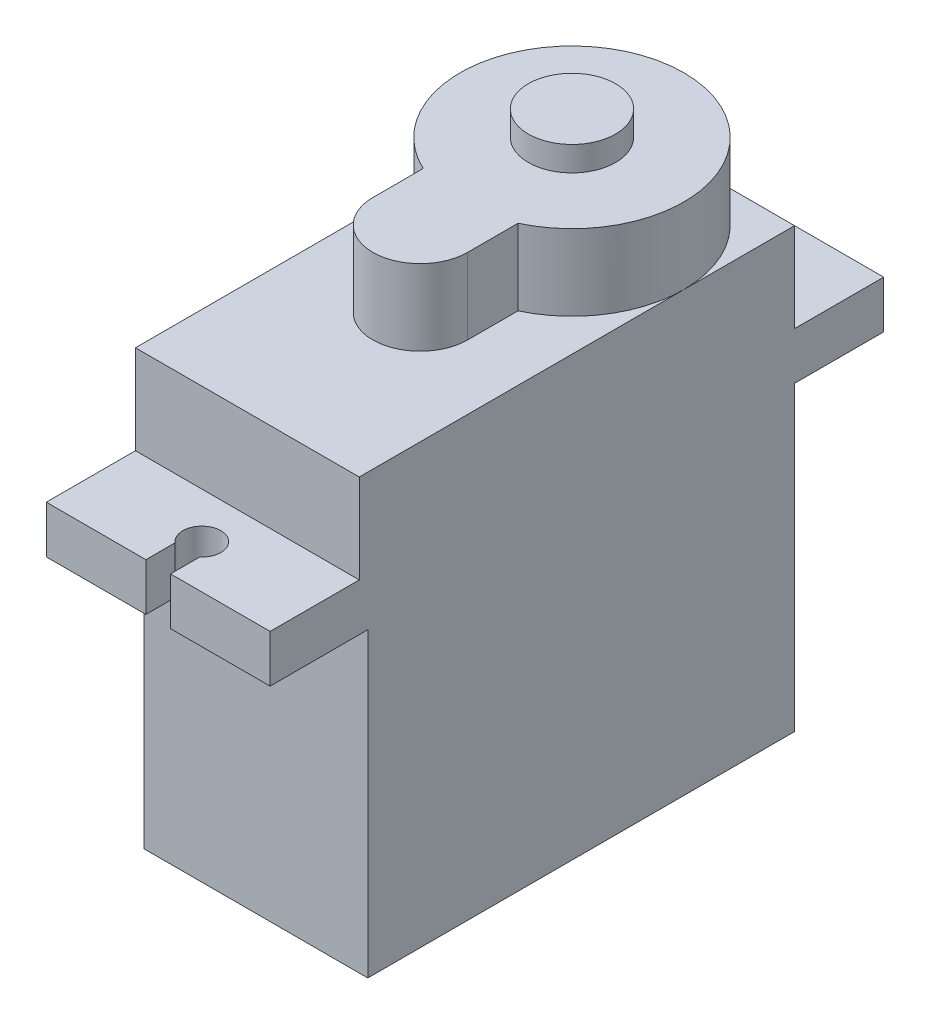
SolidWorks part; units mm, degrees
ref_plane "Front Plane" through (0, 0, 0) normal (0, 0, 1) x (1, 0, 0)
ref_plane "Top Plane" through (0, 0, 0) normal (0, 1, 0) x (1, 0, 0)
ref_plane "Right Plane" through (0, 0, 0) normal (1, 0, 0) x (0, 0, -1)
sketch "Sketch2" plane through (0, 0, 0) normal (1, 0, 0) x (0, 0, -1)
  line L0 (7.4323, 0) -> (29.9323, 0)
  line L1 (29.9323, 0) -> (29.9323, 15.9)
  line L2 (29.9323, 15.9) -> (34.6323, 15.9)
  line L3 (34.6323, 15.9) -> (34.6323, 18.4)
  line L4 (34.6323, 18.4) -> (29.9323, 18.4)
  line L5 (29.9323, 18.4) -> (29.9323, 23.1)
  line L6 (29.9323, 23.1) -> (6.983, 23.1)
  line L7 (6.983, 23.1) -> (6.983, 18.4)
  line L8 (6.983, 18.4) -> (2.283, 18.4)
  line L9 (2.283, 18.4) -> (2.283, 15.9)
  line L10 (2.283, 15.9) -> (7.4323, 15.9)
  line L11 (7.4323, 15.9) -> (7.4323, 0)
  dimension "D1" = 22.5
  dimension "D2" = 15.9
  dimension "D3" = 4.7
  dimension "D4" = 2.5
  dimension "D5" = 4.7
  dimension "D6" = 4.7
  dimension "D7" = 2.5
  dimension "D8" = 15.9
extrude "Boss-Extrude1" add sketch "Sketch2" along normal blind 11.8
sketch "Sketch3" plane through (0, 23.1, 0) normal (0, 1, 0) x (-1, 0, 0)
  line L0 (-11.8, -29.9323) -> (-11.8, -6.983) construction
  line L1 (-3.4, -16.098) -> (-3.4, -18.7539)
  line L3 (-8.4, -16.098) -> (-8.4, -18.7539)
  arc A0 (-8.4, -18.7539) -> (-3.4, -18.7539) centre (-5.9, -24.098) ccw
  arc A1 (-3.4, -16.098) -> (-8.4, -16.098) centre (-5.9, -16.098) ccw
  dimension "D1" = 11.8
  dimension "D3" = 5
  dimension "D2" = 5.9
  dimension "D4" = 8
extrude "Boss-Extrude2" add sketch "Sketch3" along normal blind 4
sketch "Sketch4" plane through (0, 27.1, 0) normal (0, 1, 0) x (-1, 0, 0)
  circle A0 centre (-5.9, -24.098) radius 2.3
  dimension "D1" = 4.6
extrude "Boss-Extrude3" add sketch "Sketch4" along normal blind 3.2
sketch "Sketch5" plane through (0, 30.3, 0) normal (0, 1, 0) x (1, 0, 0)
  circle A0 centre (5.9, 24.098) radius 0.85
  dimension "D1" = 1.7
extrude "Cut-Extrude1" cut sketch "Sketch5" against normal blind 1
sketch "Sketch6" plane through (0, 18.4, 0) normal (0, 1, 0) x (1, 0, 0)
  line L0 (11.8, 2.283) -> (0, 2.283) construction
  line L1 (11.8, 34.6323) -> (0, 34.6323) construction
  line L2 (6.55, 2.283) -> (5.25, 2.283)
  line L3 (5.25, 2.283) -> (5.25, 3.823)
  line L4 (11.8, 2.283) -> (0, 2.283) construction
  line L5 (6.55, 2.283) -> (6.55, 3.823)
  line L6 (6.55, 34.6323) -> (5.25, 34.6323)
  line L7 (5.25, 34.6323) -> (5.25, 33.0922)
  line L8 (6.55, 34.6323) -> (6.55, 33.0922)
  arc A0 (5.25, 33.0922) -> (6.55, 33.0922) centre (5.9, 32.3323) ccw
  arc A1 (6.55, 3.823) -> (5.25, 3.823) centre (5.9, 4.583) ccw
  point P10 (5.9, 2.283)
  dimension "D1" = 2
  dimension "D3" = 2
  dimension "D2" = 2.3
  dimension "D4" = 2.3
  dimension "D5" = 1.3
  dimension "D6" = 0.65
extrude "Cut-Extrude2" cut sketch "Sketch6" against normal blind 10
other "Congelar***"
other "Mover face1" [suppressed] flip direction yes offset 1.7 parameters "D1"=1.7
other "Mover face2" flip direction yes face at (5.9, 30.3, -23.248) offset 1.9 parameters "D1"=1.9
ref_plane "Plano1" through (0, 17.15, 0) normal (0, -1, 0) x (-1, 0, 0)
sketch "Esboço1" plane through (0, 17.15, 0) normal (0, -1, 0) x (-1, 0, 0)
  point P0 (-5.9, 4.583)
other "PontoC1" parameters "Diâmetro"=1, "ComprimentoAdaptador"=5
ref_axis "Eixo1" through (5.9, 17.15, 5.417) along (0, 0, -1)
